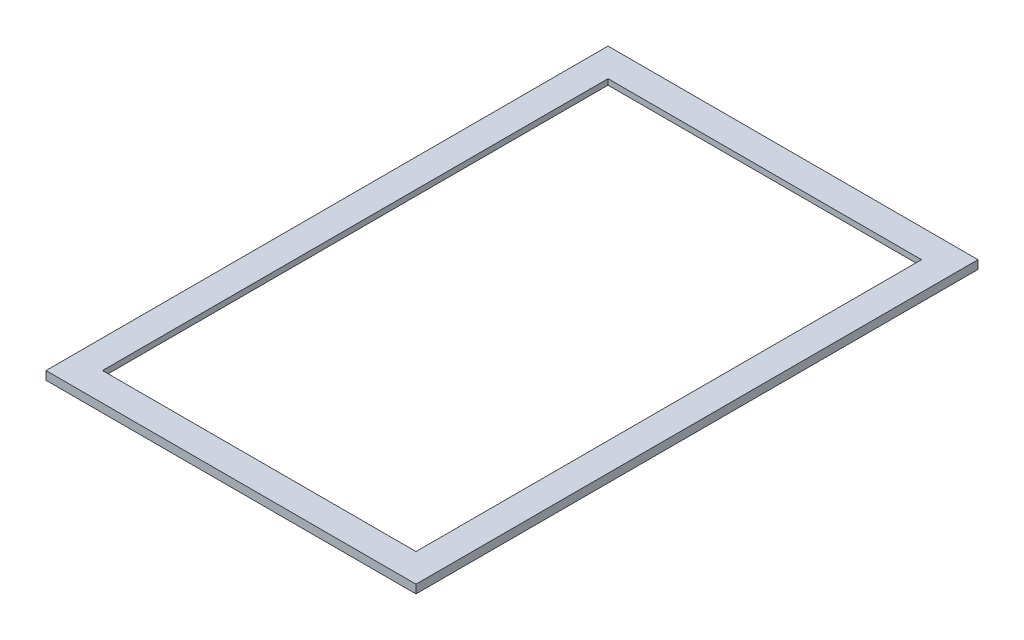
SolidWorks part; units mm, degrees
ref_plane "Спереди" through (0, 0, 0) normal (0, 0, 1) x (1, 0, 0)
ref_plane "Сверху" through (0, 0, 0) normal (0, 1, 0) x (1, 0, 0)
ref_plane "Справа" through (0, 0, 0) normal (1, 0, 0) x (0, 0, -1)
sketch "Эскиз1" plane through (0, 0, 0) normal (0, 1, 0) x (1, 0, 0)
  line L1 (-65.5, -99.5) -> (65.5, -99.5)
  line L2 (-65.5, -99.5) -> (-65.5, 99.5)
  line L3 (-65.5, 99.5) -> (65.5, 99.5)
  line L4 (65.5, -99.5) -> (65.5, 99.5)
  line L5 (-65.5, -99.5) -> (65.5, 99.5) construction
  line L6 (-65.5, 99.5) -> (65.5, -99.5) construction
  point P0 (0, 0)
  dimension "D1" = 199
  dimension "D2" = 131
extrude "Бобышка-Вытянуть1" add sketch "Эскиз1" along normal blind 3
sketch "Эскиз2" plane through (0, 3, 0) normal (0, 1, 0) x (1, 0, 0)
  line L0 (65.5, 99.5) -> (-65.5, 99.5) construction
  line L1 (-55.5, -89.5) -> (55.5, -89.5)
  line L2 (-55.5, -89.5) -> (-55.5, 89.5)
  line L3 (-55.5, 89.5) -> (55.5, 89.5)
  line L4 (55.5, -89.5) -> (55.5, 89.5)
  line L5 (-55.5, -89.5) -> (55.5, 89.5) construction
  line L6 (-55.5, 89.5) -> (55.5, -89.5) construction
  line L7 (65.5, -99.5) -> (65.5, 99.5) construction
  point P0 (0, 0)
  dimension "D1" = 10
  dimension "D2" = 10
extrude "Вырез-Вытянуть1" cut sketch "Эскиз2" against normal blind 6
sketch "Эскиз3" plane through (0, 0, 0) normal (0, -1, 0) x (1, 0, 0)
  line L0 (-55.5, 89.5) -> (55.5, 89.5) construction
  line L1 (-58.8295, -94.5) -> (58.8295, -94.5)
  line L2 (-58.8295, -94.5) -> (-58.8295, 94.5)
  line L3 (-58.8295, 94.5) -> (58.8295, 94.5)
  line L4 (58.8295, -94.5) -> (58.8295, 94.5)
  line L5 (-58.8295, -94.5) -> (58.8295, 94.5) construction
  line L6 (-58.8295, 94.5) -> (58.8295, -94.5) construction
  line L7 (-65.5, -99.5) -> (-65.5, 99.5) construction
  point P0 (0, 0)
  dimension "D1" = 5
  dimension "D2" = 6.6705
extrude "Вырез-Вытянуть2" cut sketch "Эскиз3" against normal blind 1
